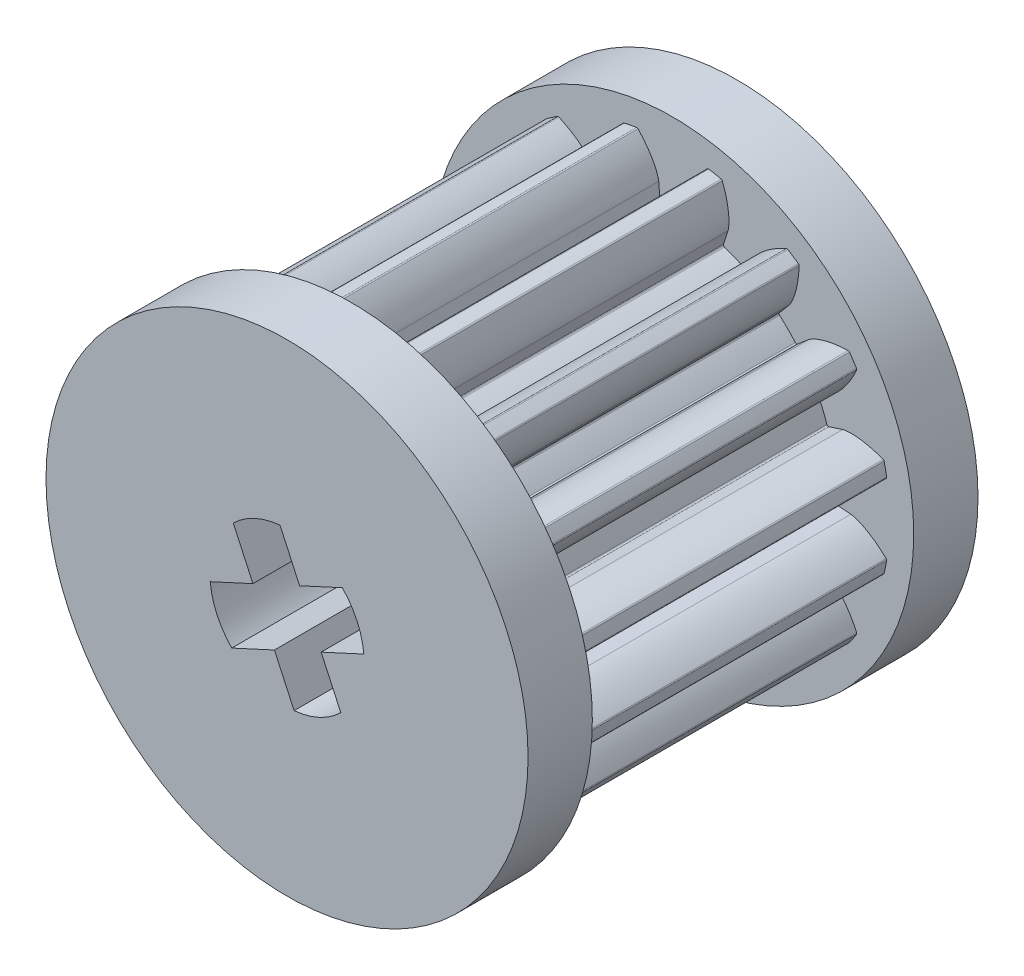
SolidWorks part; units mm, degrees
ref_plane "Front Plane" through (0, 0, 0) normal (0, 0, 1) x (1, 0, 0)
ref_plane "Top Plane" through (0, 0, 0) normal (0, 1, 0) x (1, 0, 0)
ref_plane "Right Plane" through (0, 0, 0) normal (1, 0, 0) x (0, 0, -1)
ref_axis "Axis1" [suppressed] through (0, 0, 71.2135) along (0, 0, -1)
sketch "Sketch1" plane through (0, 0, 0) normal (0, 0, 1) x (1, 0, 0)
  circle A0 centre (0, 0) radius 5.0625
  circle A1 centre (0, 0) radius 5.5631
  circle A2 centre (0, 0) radius 5.25
  circle A3 centre (0, 0) radius 6
  circle A4 centre (0, 0) radius 6.75
  dimension "Pitch" = 12
  dimension "Addendum" = 13.5
  dimension "Clearance" = 10.5
  dimension "Base" = 11.1262
  dimension "Root" = 10.125
extrude "Boss-Extrude1" add sketch "Sketch1" along normal blind 10 contours A4
sketch "Sketch3" plane through (0, 0, 0) normal (0, 0, 1) x (1, 0, 0)
  line L0 (0.4342, 5.5461) -> (0, 0) construction
  line L1 (0.868, 5.495) -> (0, 0) construction
  line L2 (1.2964, 5.4099) -> (0, 0) construction
  line L3 (1.7169, 5.2915) -> (0, 0) construction
  line L4 (2.1268, 5.1405) -> (0, 0) construction
  line L5 (2.5235, 4.9578) -> (0, 0) construction
  line L6 (2.9047, 4.7445) -> (0, 0) construction
  line L7 (3.268, 4.502) -> (0, 0) construction
  line L8 (3.6112, 4.2317) -> (0, 0) construction
  line L9 (3.9321, 3.9353) -> (0, 0) construction
  line L10 (4.2287, 3.6147) -> (0, 0) construction
  line L11 (0.868, 5.495) -> (0.4364, 5.5631) construction
  line L12 (4.2287, 3.6147) -> (1.3897, 6.9359) construction
  line L13 (1.2964, 5.4099) -> (0.4466, 5.6136) construction
  line L14 (1.7169, 5.2915) -> (0.4701, 5.6961) construction
  line L15 (2.1268, 5.1405) -> (0.5118, 5.8087) construction
  line L16 (2.5235, 4.9578) -> (0.5766, 5.9488) construction
  line L17 (2.9047, 4.7445) -> (0.6689, 6.1134) construction
  line L18 (3.268, 4.502) -> (0.7929, 6.2987) construction
  line L19 (3.6112, 4.2317) -> (0.9523, 6.5007) construction
  line L20 (3.9321, 3.9353) -> (1.1503, 6.7148) construction
  line L21 (0, 0) -> (0, 6) construction
  line L22 (0, 0) -> (0.5881, 5.9711)
  line L23 (0, 0) -> (-0.5881, 5.9711)
  line L24 (0.4342, 5.5461) -> (0.3951, 5.0471)
  line L25 (-0.4342, 5.5461) -> (-0.3951, 5.0471)
  circle A0 centre (0, 0) radius 5.5631 construction
  circle A1 centre (0, 0) radius 6 construction
  arc A2 (4.2287, 3.6147) -> (0.4342, 5.5461) centre (0, 0) ccw construction
  circle A3 centre (0, 0) radius 5.0625 construction
  circle A4 centre (0, 0) radius 5.0625
  circle A5 centre (0, 0) radius 6.75 construction
  circle A6 centre (0, 0) radius 6.75
  spline S0 degree 3 poles (0.4342, 5.5461) (0.4366, 5.5689) (0.447, 5.6194) (0.4724, 5.7074) (0.5146, 5.8199) (0.6112, 6.0273) (0.7582, 6.2606) (1.0245, 6.5969) (1.2334, 6.8022) (1.3897, 6.9359) knots 0 0 0 0 0.040008 0.090018 0.16003 0.250047 0.489907 0.639935 1 1 1 1
  spline S1 degree 3 poles (-0.4342, 5.5461) (-0.4366, 5.5689) (-0.447, 5.6194) (-0.4724, 5.7074) (-0.5146, 5.8199) (-0.6112, 6.0273) (-0.7582, 6.2606) (-1.0245, 6.5969) (-1.2334, 6.8022) (-1.3897, 6.9359) knots 0 0 0 0 0.040008 0.090018 0.16003 0.250047 0.489907 0.639935 1 1 1 1
  point P18 (0, 0)
  dimension "D2" = 45
  dimension "D3" = 0.4369
  dimension "D4" = 4.3693
  dimension "D5" = 0.8739
  dimension "D6" = 1.3108
  dimension "D7" = 1.7477
  dimension "D8" = 2.1846
  dimension "D9" = 2.6216
  dimension "D10" = 3.0585
  dimension "D11" = 3.4954
  dimension "D12" = 3.9323
  dimension "D13" = 11.25
  dimension "D1" = 11
extrude "Cut-Extrude3" cut sketch "Sketch3" along normal through all contours S1 L25 A4 L24 S0 A6 region at (0, 6.0519, 0)
fillet "Fillet2" radius 0.05 4 edges at (0.3951, 5.0471, 5) (-0.3951, 5.0471, 5) (1.0969, 6.6603, 5) (-1.0969, 6.6603, 5)
pattern_circular "CirPattern1" count 16 over 360 about axis through (0, 0, 71.2135) along (0, 0, -1) of "Cut-Extrude3", "Fillet2"
ref_plane "Plane2" through (0, 0, 5) normal (0, 0, 1) x (1, 0, 0)
sketch "Sketch6" plane through (0, 0, 10) normal (0, 0, 1) x (1, 0, 0)
  circle A0 centre (0, 0) radius 7.5
  dimension "D1" = 15
extrude "Boss-Extrude2" add sketch "Sketch6" along normal blind 2
mirror "Mirror1" about plane through (0, 0, 5) normal (0, 0, 1) of "Boss-Extrude2"
sketch "Sketch5" plane through (0, 0, 0) normal (0, 0, 1) x (1, 0, 0)
  line L0 (-2.3899, -0.2198) -> (-1.0613, 0.392) construction
  line L1 (-0.392, -1.0613) -> (-1.7206, -1.6731) construction
  line L2 (0.2198, -2.3899) -> (-0.392, -1.0613) construction
  line L3 (1.0613, -0.392) -> (1.6731, -1.7206) construction
  line L4 (2.3899, 0.2198) -> (1.0613, -0.392) construction
  line L5 (0.392, 1.0613) -> (1.7206, 1.6731) construction
  line L6 (-0.2198, 2.3899) -> (0.392, 1.0613) construction
  line L7 (-1.0613, 0.392) -> (-1.6731, 1.7206) construction
  line L8 (-2.3899, -0.2198) -> (-1.0613, 0.392)
  line L9 (-0.392, -1.0613) -> (-1.7206, -1.6731)
  line L10 (0.2198, -2.3899) -> (-0.392, -1.0613)
  line L11 (1.0613, -0.392) -> (1.6731, -1.7206)
  line L12 (2.3899, 0.2198) -> (1.0613, -0.392)
  line L13 (0.392, 1.0613) -> (1.7206, 1.6731)
  line L14 (-0.2198, 2.3899) -> (0.392, 1.0613)
  line L15 (-1.0613, 0.392) -> (-1.6731, 1.7206)
  arc A0 (-2.3899, -0.2198) -> (-1.7206, -1.6731) centre (0, 0) ccw construction
  arc A1 (0.2198, -2.3899) -> (1.6731, -1.7206) centre (0, 0) ccw construction
  arc A2 (2.3899, 0.2198) -> (1.7206, 1.6731) centre (0, 0) ccw construction
  arc A3 (-0.2198, 2.3899) -> (-1.6731, 1.7206) centre (0, 0) ccw construction
  arc A4 (-2.3899, -0.2198) -> (-1.7206, -1.6731) centre (0, 0) ccw
  arc A5 (0.2198, -2.3899) -> (1.6731, -1.7206) centre (0, 0) ccw
  arc A6 (2.3899, 0.2198) -> (1.7206, 1.6731) centre (0, 0) ccw
  arc A7 (-0.2198, 2.3899) -> (-1.6731, 1.7206) centre (0, 0) ccw
extrude "Cut-Extrude4" cut sketch "Sketch5" along normal through all both and the other way through all
equation "\"Module\"= .75"
equation "\"numTeeth\"= 16"
equation "\"pressureAngle\"= 22deg"
equation "\"toothRadius\"= .05"
equation "\"Pitch@Sketch1\"=\"Module\"*\"numTeeth\""
equation "\"Addendum@Sketch1\"=\"Pitch@Sketch1\"+\"Module\"*2"
equation "\"Clearance@Sketch1\"=\"Pitch@Sketch1\"-\"Module\"*2"
equation "\"Base@Sketch1\"=\"Pitch@Sketch1\"*cos(\"pressureAngle\")"
equation "\"Root@Sketch1\"=\"Pitch@Sketch1\"-\"Module\"*1.25*2"
equation "\"D4@Sketch3\"= \"Base@Sketch1\" * pi / 8"
equation "\"D3@Sketch3\"= \"D4@Sketch3\" / 10"
equation "\"D5@Sketch3\"=\"D3@Sketch3\"*2"
equation "\"D6@Sketch3\"=\"D3@Sketch3\"*3"
equation "\"D7@Sketch3\"=\"D3@Sketch3\"*4"
equation "\"D8@Sketch3\"=\"D3@Sketch3\"*5"
equation "\"D9@Sketch3\"=\"D3@Sketch3\"*6"
equation "\"D10@Sketch3\"=\"D3@Sketch3\"*7"
equation "\"D11@Sketch3\"=\"D3@Sketch3\"*8"
equation "\"D12@Sketch3\"=\"D3@Sketch3\"*9"
equation "\"D13@Sketch3\"=180/\"numTeeth\""
equation "\"D1@CirPattern1\"=\"numTeeth\""
equation "\"D1@Fillet2\"= \"toothRadius\""
